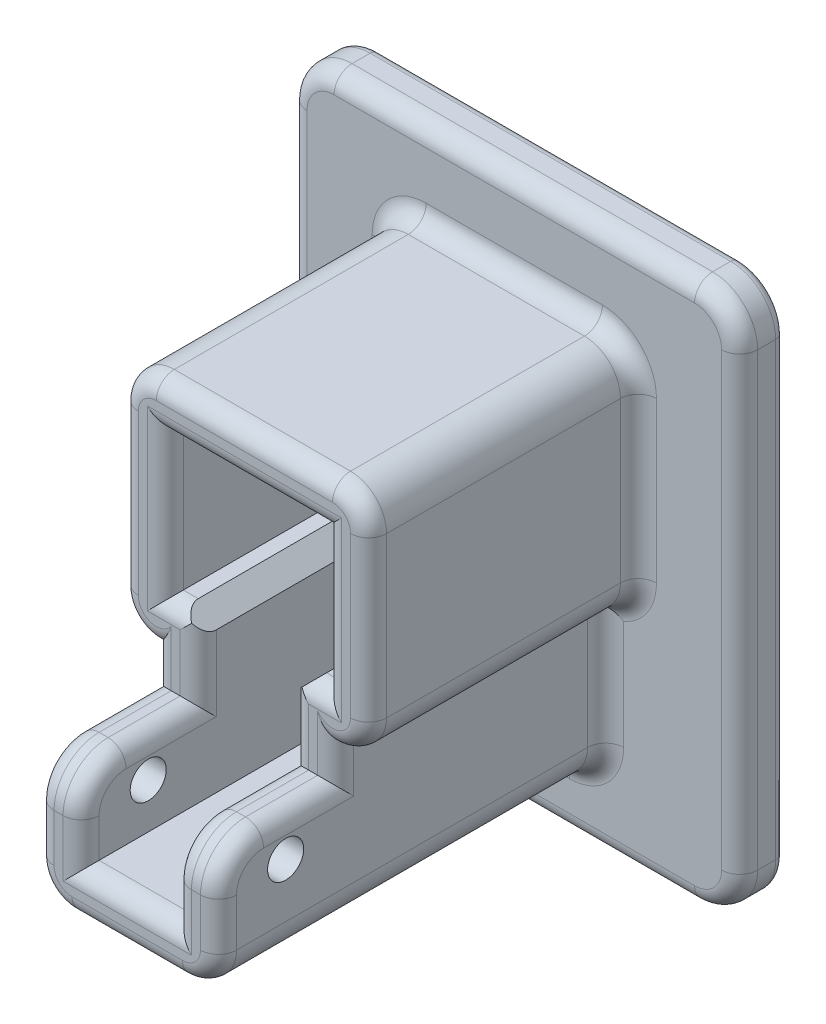
SolidWorks part; units mm, degrees
ref_plane "Ebene vorne" through (0, 0, 0) normal (0, 0, 1) x (1, 0, 0)
ref_plane "Ebene oben" through (0, 0, 0) normal (0, 1, 0) x (1, 0, 0)
ref_plane "Ebene rechts" through (0, 0, 0) normal (1, 0, 0) x (0, 0, -1)
sketch "Skizze1" plane through (0, 0, 0) normal (0, 0, 1) x (1, 0, 0)
  line L0 (0, 31.2062) -> (0, -25.9494) construction
  line L1 (-5.125, -17.65) -> (5.125, -17.65)
  line L2 (5.125, -17.65) -> (5.125, 0)
  line L3 (5.125, 0) -> (8.775, 0)
  line L4 (8.775, 0) -> (8.775, 15.7)
  line L5 (8.775, 15.7) -> (-8.775, 15.7)
  line L6 (4.0086, 0) -> (-5.5264, 0) construction
  line L7 (-5.125, -17.65) -> (-5.125, 0)
  line L8 (-5.125, 0) -> (-8.775, 0)
  line L9 (-8.775, 0) -> (-8.775, 15.7)
  line L10 (-10.125, -22.65) -> (10.125, -22.65)
  line L11 (10.125, -22.65) -> (10.125, -5)
  line L12 (10.125, -5) -> (13.775, -5)
  line L13 (13.775, -5) -> (13.775, 20.7)
  line L14 (13.775, 20.7) -> (-13.775, 20.7)
  line L15 (-10.125, -22.65) -> (-10.125, -5)
  line L16 (-10.125, -5) -> (-13.775, -5)
  line L17 (-13.775, -5) -> (-13.775, 20.7)
  point P13 (0, -17.65)
  point P16 (0, 15.7)
  point P22 (0, -22.65)
  point P25 (0, 20.7)
  dimension "D1" = 5.125
  dimension "D2" = 8.775
  dimension "D3" = 17.65
  dimension "D4" = 15.7
  dimension "D5" = 5
  dimension "D6" = 5
  dimension "D7" = 5
  dimension "D8" = 5
  dimension "D9" = 5
extrude "Aufsatz-Linear austragen1" add sketch "Skizze1" along normal blind 29.95
sketch "Skizze2" plane through (0, 0, 29.95) normal (0, 0, 1) x (1, 0, 0)
  line L0 (5.125, -17.65) -> (5.125, -8.35)
  line L2 (5.125, -17.65) -> (5.125, 0) construction
  line L4 (5.125, -8.35) -> (10.125, -8.35)
  line L5 (10.125, -22.65) -> (10.125, -5) construction
  line L6 (10.125, -8.35) -> (10.125, -22.65)
  line L8 (10.125, -22.65) -> (-10.125, -22.65)
  line L10 (-10.125, -22.65) -> (10.125, -22.65) construction
  line L11 (-10.125, -22.65) -> (-10.125, -8.35)
  line L12 (-10.125, -5) -> (-10.125, -22.65) construction
  line L13 (-10.125, -8.35) -> (-5.125, -8.35)
  line L14 (-5.125, 0) -> (-5.125, -17.65) construction
  line L15 (-5.125, -8.35) -> (-5.125, -17.65)
  line L16 (-5.125, -17.65) -> (5.125, -17.65) construction
  line L17 (-5.125, -17.65) -> (5.125, -17.65)
  point P2 (-10.025, -22.55)
  point P5 (-9.406, -22.55)
  dimension "D1" = 9.3
extrude "Aufsatz-Linear austragen2" add sketch "Skizze2" along normal blind 13
sketch "Skizze4" plane through (-5.125, 0, 0) normal (1, 0, 0) x (0, 0, -1)
  line L0 (-42.95, -17.65) -> (0, -17.65) construction
  line L1 (0, 0) -> (0, -17.65) construction
  circle A0 centre (-35.5, -12.65) radius 2
  dimension "D1" = 5
  dimension "D2" = 4
  dimension "D3" = 35.5
extrude "Schnitt-Linear austragen1" cut sketch "Skizze4" against normal mid plane 40
sketch "Skizze5" plane through (0, 0, 0) normal (0, 0, -1) x (-1, 0, 0)
  line L1 (-25, 30) -> (25, 30)
  line L2 (-25, 30) -> (-25, -30)
  line L3 (-25, -30) -> (25, -30)
  line L4 (25, 30) -> (25, -30)
  line L5 (-25, 30) -> (25, -30) construction
  line L6 (-25, -30) -> (25, 30) construction
  point P0 (0, 0)
  dimension "D1" = 60
  dimension "D2" = 50
extrude "Aufsatz-Linear austragen3" add sketch "Skizze5" along normal blind 5
chamfer "Fase1" distance 2 angle 45 2 edges at (5.125, 0, 14.975) (-5.125, 0, 14.975)
fillet "Verrundung1" radius 5 2 edges at (-7.625, -8.35, 42.95) (7.625, -8.35, 42.95)
fillet "Verrundung4" radius 4 6 edges at (13.775, -5, 14.975) (13.775, 20.7, 14.975) (10.125, -22.65, 21.475) (-10.125, -22.65, 21.475) (-13.775, -5, 14.975) (-13.775, 20.7, 14.975)
fillet "Verrundung7" radius 5 4 edges at (-25, -30, -2.5) (25, -30, -2.5) (-25, 30, -2.5) (25, 30, -2.5)
fillet "Verrundung5" radius 2 20 edges at (0, 30, 0) (25, 0, 0) (0, -30, 0) (-25, 0, 0) (-8.9534, -21.4784, 0) (0, -22.65, 0) (8.9534, -21.4784, 0) (10.125, -11.825, 0) (12.7246, -3.7172, 0) (13.775, 7.8423, 0) (12.6034, 19.5284, 0) (0, 20.7, 0) (-12.6034, 19.5284, 0) (-13.775, 7.8423, 0) (-12.7246, -3.7172, 0) (-10.125, -11.825, 0) (-23.5355, 28.5355, 0) (23.5355, 28.5355, 0) (23.5355, -28.5355, 0) (-23.5355, -28.5355, 0)
fillet "Verrundung8" radius 1 8 edges at (23.5355, -28.5355, -5) (25, 0, -5) (23.5355, 28.5355, -5) (0, 30, -5) (-23.5355, 28.5355, -5) (-25, 0, -5) (-23.5355, -28.5355, -5) (0, -30, -5)
fillet "Verrundung9" radius 2 14 edges at (5.125, -15.5, 42.95) (-5.125, -15.5, 42.95) (5.125, -9.8145, 41.4855) (-5.125, -9.8145, 41.4855) (5.125, -8.35, 33.95) (-5.125, -8.35, 33.95) (5.125, -5.175, 29.95) (7.95, 0, 29.95) (8.775, 7.85, 29.95) (0, 15.7, 29.95) (-8.775, 7.85, 29.95) (-7.95, 0, 29.95) (-5.125, -5.175, 29.95) (0, -17.65, 42.95)
fillet "Verrundung12" radius 2 12 edges at (-12.7246, -3.7172, 29.95) (-13.775, 7.8423, 29.95) (0, 20.7, 29.95) (12.7246, -3.7172, 29.95) (13.775, 7.8423, 29.95) (10.125, -6.675, 29.95) (10.125, -8.35, 33.95) (-10.125, -8.35, 33.95) (-10.125, -16, 42.95) (0, -22.65, 42.95) (10.125, -16, 42.95) (-10.125, -6.675, 29.95) tangent propagation no
